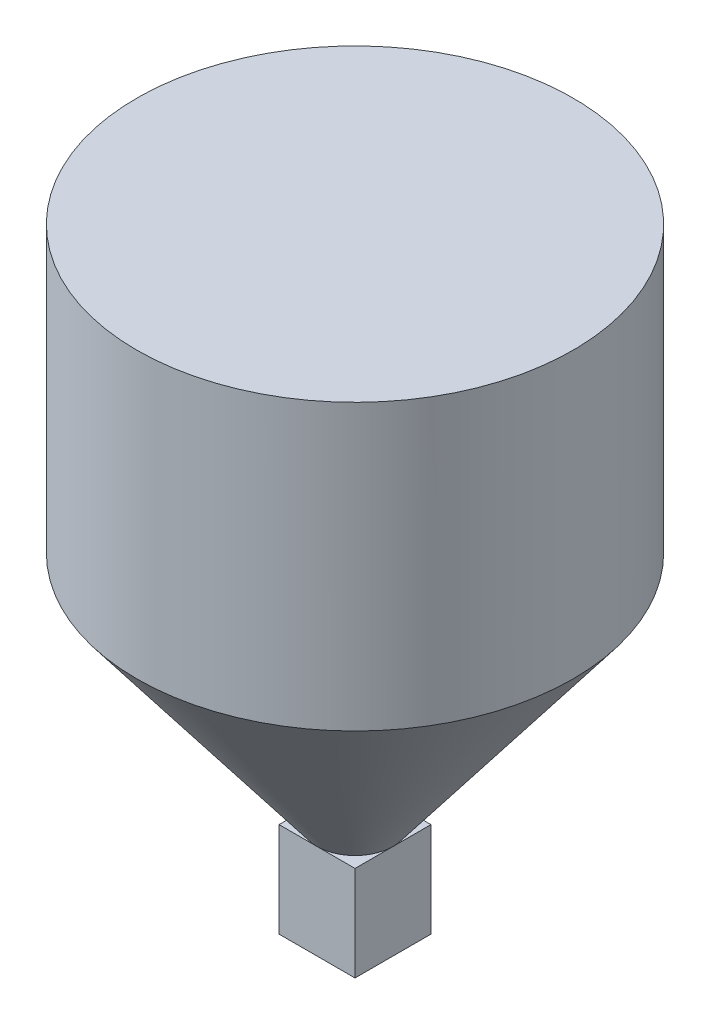
SolidWorks part; units mm, degrees
ref_plane "Alzado" through (0, 0, 0) normal (0, 0, 1) x (1, 0, 0)
ref_plane "Planta" through (0, 0, 0) normal (0, 1, 0) x (1, 0, 0)
ref_plane "Vista lateral" through (0, 0, 0) normal (1, 0, 0) x (0, 0, -1)
sketch "Croquis1" plane through (0, 0, 0) normal (0, 1, 0) x (1, 0, 0)
  circle A0 centre (0, 0) radius 115
  dimension "D1" = 230
ref_plane "Plano1" through (0, -274, 0) normal (0, 1, 0) x (1, 0, 0)
extrude "Saliente-Extruir1" add sketch "Croquis1" against normal blind 150 contours A0
sketch "Croquis2" plane through (0, -150, 0) normal (0, -1, 0) x (1, 0, 0)
  circle A1 centre (0, 0) radius 115
sketch "Croquis3" plane through (0, -274, 0) normal (0, 1, 0) x (1, 0, 0)
  circle A0 centre (0, 0) radius 20
  dimension "D1" = 40
loft "Recubrir1" add profiles "Croquis3", "Croquis2" connector at (-19.9701, -274, 1.0927) connector at (-114.7731, -150, 7.2209)
sketch "Croquis4" plane through (0, -274, 0) normal (0, -1, 0) x (1, 0, 0)
  line L1 (-20, -20) -> (20, -20)
  line L2 (-20, -20) -> (-20, 20)
  line L3 (-20, 20) -> (20, 20)
  line L4 (20, -20) -> (20, 20)
  line L5 (-20, -20) -> (20, 20) construction
  line L6 (-20, 20) -> (20, -20) construction
  point P0 (0, 0)
  dimension "D1" = 40
  dimension "D2" = 40
extrude "Saliente-Extruir2" add sketch "Croquis4" along normal blind 50
